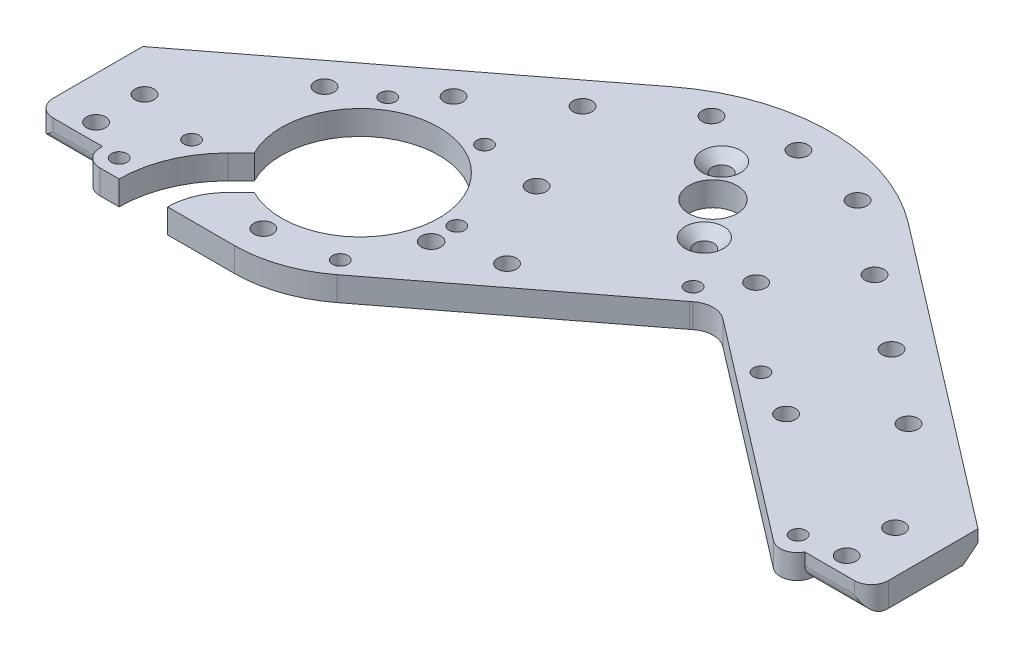
SolidWorks part; units mm, degrees
material "Alum Plate"
ref_plane "Front Plane" through (0, 0, 0) normal (0, 0, 1) x (1, 0, 0)
ref_plane "Top Plane" through (0, 0, 0) normal (0, 1, 0) x (1, 0, 0)
ref_plane "Right Plane" through (0, 0, 0) normal (1, 0, 0) x (0, 0, -1)
sketch "Top Layout" plane through (0, 0, 0) normal (0, 1, 0) x (1, 0, 0)
  line L0 (-114.046, -123.825) -> (-104.775, -123.825) construction
  line L1 (-104.775, -142.875) -> (-101.6, -142.875)
  line L2 (-104.775, -142.875) -> (-104.775, -104.775)
  line L3 (-104.775, -104.775) -> (-101.6, -104.775)
  line L4 (-101.6, -142.875) -> (-101.6, -104.775)
  line L5 (-104.775, -142.875) -> (-101.6, -104.775) construction
  line L6 (-104.775, -104.775) -> (-101.6, -142.875) construction
  line L7 (-19.05, -105.8164) -> (-101.6, -105.8164)
  line L8 (-19.05, -105.8164) -> (-19.05, -141.8336)
  line L9 (-19.05, -141.8336) -> (-101.6, -141.8336)
  line L10 (-101.6, -105.8164) -> (-101.6, -141.8336)
  line L11 (-19.05, -105.8164) -> (-101.6, -141.8336) construction
  line L12 (-19.05, -141.8336) -> (-101.6, -105.8164) construction
  line L13 (-133.096, -85.725) -> (-114.046, -85.725)
  line L14 (-133.096, -85.725) -> (-133.096, -161.925)
  line L15 (-133.096, -161.925) -> (-114.046, -161.925)
  line L16 (-114.046, -85.725) -> (-114.046, -161.925)
  line L17 (-133.096, -85.725) -> (-114.046, -161.925) construction
  line L18 (-133.096, -161.925) -> (-114.046, -85.725) construction
  line L19 (-104.775, -123.825) -> (0, -123.825) construction
  line L20 (0, -123.825) -> (0, 0) construction
  line L21 (-52.3528, -40.1717) -> (0, 0) construction
  line L22 (-70.6449, -16.3328) -> (-18.2922, 23.8388)
  line L23 (-34.0606, -64.0105) -> (18.2922, -23.8388)
  line L24 (-30.9251, 40.3023) -> (-122.2248, -29.7544)
  line L25 (-153.9748, -53.975) -> (-153.9748, -123.825)
  line L26 (-109.5248, -162.052) -> (109.5248, -162.052)
  line L27 (0, -162.052) -> (0, -123.825) construction
  line L28 (-109.5248, -162.052) -> (-109.5248, -20.0093) construction
  line L29 (-104.775, -142.875) -> (-104.775, -152.527)
  line L30 (-104.775, -152.527) -> (104.775, -152.527)
  line L31 (104.775, -104.775) -> (101.6, -104.775)
  line L32 (-144.4498, -73.025) -> (-109.5248, -73.025)
  line L33 (-144.4498, -73.025) -> (-144.4498, -123.825)
  line L34 (-144.4498, -123.825) -> (-109.5248, -123.825) construction
  line L35 (-109.5248, -73.025) -> (-109.5248, -162.052)
  line L36 (-144.4498, -73.025) -> (-109.5248, -123.825) construction
  line L37 (-144.4498, -123.825) -> (-109.5248, -73.025) construction
  line L38 (101.6, -142.875) -> (101.6, -104.775)
  line L39 (104.775, -142.875) -> (101.6, -142.875)
  line L40 (104.775, -142.875) -> (104.775, -104.775)
  line L41 (104.775, -142.875) -> (104.775, -152.527)
  line L42 (109.5248, -162.052) -> (109.5248, -20.0093) construction
  line L43 (30.9251, 40.3023) -> (122.2248, -29.7544)
  line L45 (19.05, -141.8336) -> (101.6, -141.8336)
  line L46 (101.6, -105.8164) -> (101.6, -141.8336)
  line L47 (19.05, -105.8164) -> (101.6, -105.8164)
  line L48 (19.05, -105.8164) -> (19.05, -141.8336)
  line L49 (133.096, -161.925) -> (114.046, -161.925)
  line L50 (114.046, -85.725) -> (114.046, -161.925)
  line L51 (133.096, -85.725) -> (114.046, -85.725)
  line L52 (133.096, -85.725) -> (133.096, -161.925)
  line L53 (144.4498, -123.825) -> (109.5248, -123.825) construction
  line L54 (109.5248, -73.025) -> (109.5248, -162.052)
  line L55 (144.4498, -73.025) -> (109.5248, -73.025)
  line L56 (144.4498, -73.025) -> (144.4498, -123.825)
  line L57 (-109.5248, -123.825) -> (-109.5248, -162.052) construction
  line L62 (-153.9748, -53.975) -> (-122.2248, -53.975)
  line L63 (-122.2248, -53.975) -> (-122.2248, -29.7544)
  line L64 (-144.4498, -123.825) -> (-153.9748, -123.825)
  line L65 (153.9748, -53.975) -> (153.9748, -123.825)
  line L66 (109.5248, -123.825) -> (109.5248, -162.052) construction
  line L67 (144.4498, -123.825) -> (153.9748, -123.825)
  line L68 (122.2248, -29.7544) -> (122.2248, -53.975)
  line L73 (-104.775, -104.775) -> (-104.775, -16.3647) construction
  line L74 (-95.25, -162.052) -> (-95.25, -9.0559) construction
  line L75 (-109.5248, -162.052) -> (-109.5248, -123.825) construction
  line L76 (109.5248, -162.052) -> (109.5248, -123.825) construction
  line L77 (122.2248, -53.975) -> (153.9748, -53.975)
  line L83 (104.775, -155.5496) -> (-104.775, -155.5496) construction
  line L88 (95.25, -162.052) -> (95.25, -9.0559) construction
  line L89 (104.775, -104.775) -> (104.775, -16.3647) construction
  line L92 (-104.775, -152.527) -> (-104.775, -162.052) construction
  line L93 (-14.605, -76.327) -> (14.605, -76.327)
  line L94 (-14.605, -76.327) -> (-14.605, -152.527)
  line L95 (-14.605, -152.527) -> (14.605, -152.527)
  line L96 (14.605, -76.327) -> (14.605, -152.527)
  line L97 (-14.605, -76.327) -> (14.605, -152.527) construction
  line L98 (-14.605, -152.527) -> (14.605, -76.327) construction
  line L99 (104.775, -152.527) -> (104.775, -162.052) construction
  line L100 (-19.05, -105.8164) -> (0, -105.8164) construction
  line L107 (0, -105.8164) -> (19.05, -105.8164) construction
  line L108 (104.775, -123.825) -> (114.046, -123.825) construction
  circle A0 centre (0, 0) radius 114.3
  circle A1 centre (0, 0) radius 6.35
  circle A2 centre (-52.3528, -40.1717) radius 17.8
  circle A3 centre (0, 0) radius 30.0482
  circle A4 centre (-52.3528, -40.1717) radius 30.0482
  arc A5 (-30.9251, 40.3023) -> (30.9251, 40.3023) centre (0, 0) cw
  point P2 (-103.1875, -123.825)
  point P7 (-60.325, -123.825)
  point P12 (-123.571, -123.825)
  point P30 (-126.9873, -98.425)
  point P35 (0, -114.427)
  point P53 (0, -152.527)
  dimension "D1" = 35.6
  dimension "D2" = 12.7
  dimension "D3" = 228.6
  dimension "D11" = 60.0964
  dimension "D12" = 50.8
  dimension "D14" = 52.5
  dimension "D4" = 3.175
  dimension "D5" = 19.05
  dimension "D6" = 76.2
  dimension "D7" = 82.55
  dimension "D8" = 38.1
  dimension "D9" = 104.775
  dimension "D10" = 18.0086
  dimension "D13" = 9.525
  dimension "D15" = 4.7498
  dimension "D16" = 9.525
  dimension "D17" = 9.652
  dimension "D18" = 50.8
  dimension "D19" = 12.446
  dimension "D20" = 65.9892
  dimension "D21" = 19.05
  dimension "D22" = 34.925
  dimension "D23" = 123.825
  dimension "D24" = 12.7
  dimension "D25" = 9.525
  dimension "D26" = 29.21
  dimension "D27" = 76.2
  dimension "D28" = 3.0226
sketch "Side Layout" plane through (0, 0, 0) normal (1, 0, 0) x (0, 0, -1)
  line L0 (0, -38.1) -> (0, 33.7344) construction
  line L1 (-114.3, -20.955) -> (114.3, -20.955)
  line L2 (-114.3, -20.955) -> (-114.3, -33.655)
  line L3 (-114.3, -33.655) -> (114.3, -33.655)
  line L4 (114.3, -20.955) -> (114.3, -33.655)
  line L5 (-114.3, -20.955) -> (114.3, -33.655) construction
  line L6 (-114.3, -33.655) -> (114.3, -20.955) construction
  line L7 (-9.525, -32.9406) -> (9.525, -32.9406)
  line L8 (-9.525, -32.9406) -> (-9.525, -38.1)
  line L9 (-9.525, -38.1) -> (9.525, -38.1)
  line L10 (9.525, -32.9406) -> (9.525, -38.1)
  line L11 (-9.525, -32.9406) -> (9.525, -38.1) construction
  line L12 (-9.525, -38.1) -> (9.525, -32.9406) construction
  line L13 (-11.9126, -29.3338) -> (11.9126, -29.3338)
  line L14 (-11.9126, -29.3338) -> (-11.9126, -32.9406)
  line L15 (-11.9126, -32.9406) -> (11.9126, -32.9406)
  line L16 (11.9126, -29.3338) -> (11.9126, -32.9406)
  line L17 (-11.9126, -29.3338) -> (11.9126, -32.9406) construction
  line L18 (-11.9126, -32.9406) -> (11.9126, -29.3338) construction
  line L19 (-6.35, -32.9406) -> (6.35, -32.9406)
  line L20 (-6.35, -32.9406) -> (-6.35, 33.7344)
  line L21 (-6.35, 33.7344) -> (6.35, 33.7344)
  line L22 (6.35, -32.9406) -> (6.35, 33.7344)
  line L23 (-6.35, -32.9406) -> (6.35, 33.7344) construction
  line L24 (-6.35, 33.7344) -> (6.35, -32.9406) construction
  line L25 (-162.052, 0) -> (-123.825, 0) construction
  line L26 (114.3, -33.655) -> (114.3, 0) construction
  line L27 (-142.875, 19.05) -> (-104.775, 19.05)
  line L28 (-40.1717, -9.525) -> (-40.1717, 5.4) construction
  line L29 (-142.875, 19.05) -> (-142.875, -19.05)
  line L30 (-142.875, -19.05) -> (-104.775, -19.05)
  line L31 (-104.775, 19.05) -> (-104.775, -19.05)
  line L32 (-142.875, 19.05) -> (-104.775, -19.05) construction
  line L33 (-142.875, -19.05) -> (-104.775, 19.05) construction
  line L34 (-130.175, -38.1) -> (-117.9516, -38.1) construction
  line L35 (-57.9717, -14.6) -> (-22.3717, -14.6)
  line L36 (-30.0482, -2.794) -> (30.0482, -2.794)
  line L37 (-30.0482, -2.794) -> (-30.0482, -20.955)
  line L38 (-30.0482, -20.955) -> (30.0482, -20.955)
  line L39 (30.0482, -2.794) -> (30.0482, -20.955)
  line L40 (-30.0482, -2.794) -> (30.0482, -20.955) construction
  line L41 (-30.0482, -20.955) -> (30.0482, -2.794) construction
  line L42 (-30.0482, -2.794) -> (-30.0482, 0) construction
  line L43 (-123.825, 0) -> (0, 0) construction
  line L44 (-57.9717, -14.6) -> (-57.9717, 25.4)
  line L45 (-57.9717, 25.4) -> (-22.3717, 25.4)
  line L46 (-22.3717, -14.6) -> (-22.3717, 25.4)
  line L47 (-19.05, 0) -> (19.05, 0)
  line L48 (-19.05, 0) -> (-19.05, -1.9812)
  line L49 (-19.05, -1.9812) -> (19.05, -1.9812)
  line L50 (19.05, 0) -> (19.05, -1.9812)
  line L51 (-19.05, 0) -> (19.05, -1.9812) construction
  line L52 (-19.05, -1.9812) -> (19.05, 0) construction
  line L53 (-70.2199, -3.175) -> (-10.1235, -3.175)
  line L54 (-70.2199, -3.175) -> (-70.2199, -15.875)
  line L55 (-70.2199, -15.875) -> (-10.1235, -15.875)
  line L56 (-10.1235, -3.175) -> (-10.1235, -15.875)
  line L57 (-70.2199, -3.175) -> (-10.1235, -15.875) construction
  line L58 (-70.2199, -15.875) -> (-10.1235, -3.175) construction
  line L59 (-40.1717, -9.525) -> (-40.1717, 0) construction
  line L60 (-57.9717, -14.6) -> (-22.3717, 25.4) construction
  line L61 (-57.9717, 25.4) -> (-22.3717, -14.6) construction
  line L62 (-22.3717, 0) -> (-57.9717, 0) construction
  line L63 (-137.8162, 0) -> (-123.825, -13.9912) construction
  line L64 (-139.065, 15.24) -> (-108.585, 15.24) construction
  line L65 (-139.065, 15.24) -> (-139.065, -15.24) construction
  line L66 (-139.065, -15.24) -> (-108.585, -15.24) construction
  line L67 (-108.585, 15.24) -> (-108.585, -15.24) construction
  line L68 (-139.065, 15.24) -> (-108.585, -15.24) construction
  line L69 (-139.065, -15.24) -> (-108.585, 15.24) construction
  line L70 (-137.8162, 0) -> (-123.825, 13.9912) construction
  line L71 (-123.825, -13.9912) -> (-109.8338, 0) construction
  line L72 (-123.825, 13.9912) -> (-109.8338, 0) construction
  line L73 (-137.8162, 0) -> (-109.8338, 0) construction
  line L74 (-123.825, -13.9912) -> (-123.825, 13.9912) construction
  line L75 (-6.35, 17.8594) -> (6.35, 17.8594)
  line L76 (114.3, 0) -> (-114.3, 0) construction
  line L77 (-22.3717, 19.05) -> (-6.35, 19.05) construction
  line L78 (-123.825, 38.1) -> (-97.9206, 38.1) construction
  line L79 (-19.05, -3.5814) -> (19.05, -3.5814)
  line L80 (-19.05, -3.5814) -> (-19.05, -1.9812)
  line L81 (-19.05, -1.9812) -> (19.05, -1.9812)
  line L82 (19.05, -3.5814) -> (19.05, -1.9812)
  line L83 (-19.05, -3.5814) -> (19.05, -1.9812) construction
  line L84 (-19.05, -1.9812) -> (19.05, -3.5814) construction
  line L85 (-8.7376, -16.7608) -> (8.7376, -16.7608)
  line L86 (-8.7376, -16.7608) -> (-8.7376, -29.3338)
  line L87 (-8.7376, -29.3338) -> (8.7376, -29.3338)
  line L88 (8.7376, -16.7608) -> (8.7376, -29.3338)
  line L89 (-8.7376, -16.7608) -> (8.7376, -29.3338) construction
  line L90 (-8.7376, -29.3338) -> (8.7376, -16.7608) construction
  line L91 (-8.7376, -3.5814) -> (8.7376, -3.5814)
  line L92 (-8.7376, -3.5814) -> (-8.7376, -16.1544)
  line L93 (-8.7376, -16.1544) -> (8.7376, -16.1544)
  line L94 (8.7376, -3.5814) -> (8.7376, -16.1544)
  line L95 (-8.7376, -3.5814) -> (8.7376, -16.1544) construction
  line L96 (-8.7376, -16.1544) -> (8.7376, -3.5814) construction
  circle A0 centre (-123.825, 0) radius 18.0086
  circle A1 centre (-123.825, 0) radius 38.1
  circle A2 centre (-139.065, 15.24) radius 1.905
  circle A3 centre (-108.585, 15.24) radius 1.905
  circle A4 centre (-108.585, -15.24) radius 1.905
  circle A5 centre (-139.065, -15.24) radius 1.905
  circle A6 centre (-137.8162, 0) radius 1.6002
  circle A7 centre (-123.825, 13.9912) radius 1.6002
  circle A8 centre (-109.8338, 0) radius 1.6002
  circle A9 centre (-123.825, -13.9912) radius 1.6002
  point P0 (0, -27.305)
  point P6 (0, -31.1372)
  point P7 (0, -35.5203)
  point P21 (0, 0.3969)
  point P32 (0, -11.8745)
  point P43 (0, -0.9906)
  point P55 (-40.1717, -9.525)
  point P72 (-40.1717, 5.4)
  point P88 (0, -23.0473)
  point P93 (0, -2.7813)
  point P102 (0, -9.8679)
  dimension "D17" = 3.81
  dimension "D18" = 3.2004
  dimension "D1" = 12.7
  dimension "D2" = 5.1594
  dimension "D3" = 19.05
  dimension "D4" = 3.6068
  dimension "D5" = 23.8252
  dimension "D6" = 12.7
  dimension "D7" = 18.161
  dimension "D8" = 1.9812
  dimension "D9" = 12.7
  dimension "D10" = 40
  dimension "D11" = 25.4
  dimension "D12" = 50.8
  dimension "D13" = 41.275
  dimension "D14" = 30.48
  dimension "D15" = 4.445
  dimension "D16" = 19.7866
  dimension "D19" = 15.875
  dimension "D20" = 6.35
  dimension "D21" = 38.1
  dimension "D22" = 1.6002
  dimension "D23" = 38.1
  dimension "D24" = 17.4752
  dimension "D25" = 12.573
ref_plane "Plane1" through (0, 25.4, 0) normal (0, 1, 0) x (1, 0, 0)
sketch "Sketch3" plane through (0, 25.4, 0) normal (0, 1, 0) x (1, 0, 0)
  line L0 (-104.775, -36.3747) -> (-30.9251, 20.2924)
  line L1 (-104.775, -104.775) -> (-104.775, -16.3647) construction
  line L2 (0, -200130.175) -> (0, 199882.0484) construction
  line L3 (-30.9251, 40.3023) -> (-122.2248, -29.7544) construction
  line L5 (-104.775, -36.3747) -> (-104.775, -77.6497)
  line L6 (-92.075, -77.6497) -> (-104.775, -77.6497)
  line L7 (30.9251, 20.2924) -> (104.775, -36.3747)
  line L8 (104.775, -77.6497) -> (92.075, -77.6497)
  line L9 (104.775, -36.3747) -> (104.775, -77.6497)
  line L11 (104.775, -104.775) -> (104.775, -16.3647) construction
  line L12 (30.9251, 40.3023) -> (122.2248, -29.7544) construction
  line L13 (92.075, -74.6536) -> (24.1423, -22.5271)
  line L14 (-32.2514, -66.3682) -> (20.1013, -26.1965)
  line L15 (-30.9251, 20.2924) -> (0, 44.022)
  line L16 (0, 44.022) -> (30.9251, 20.2924)
  line L17 (-92.075, -77.6497) -> (-92.075, -73.1917)
  line L19 (-92.075, -73.1917) -> (-52.3528, -73.1917)
  line L20 (92.075, -74.6536) -> (92.075, -77.6497)
  circle A1 centre (-52.3528, -40.1717) radius 20.6375
  circle A2 centre (0, 0) radius 6.35
  circle A3 centre (0, 0) radius 6.35 construction
  arc A4 (-52.3528, -73.1917) -> (-32.2514, -66.3682) centre (-52.3528, -40.1717) ccw
  arc A5 (20.1013, -26.1965) -> (24.1423, -22.5271) centre (0, 0) ccw
  arc A6 (30.9251, 20.2924) -> (-30.9251, 20.2924) centre (0, -20.01) ccw construction
  point P28 (0, 44.022)
  dimension "D1" = 33.02
  dimension "D5" = 50.8
  dimension "D7" = 41.275
  dimension "D2" = 41.275
  dimension "D3" = 34.925
  dimension "D4" = 12.7
  dimension "D6" = 38.1
extrude "Boss-Extrude1" add sketch "Sketch3" against normal blind 6.35
ref_plane "Plane3" through (-104.775, 0, 0) normal (-1, 0, 0) x (0, 0, 1)
sketch "Sketch6" plane through (-104.775, 0, 0) normal (-1, 0, 0) x (0, 0, 1)
  line L0 (162.052, -25.4) -> (162.052, 25.4)
  line L1 (162.052, 25.4) -> (77.6497, 25.4)
  line L2 (36.3747, 25.4) -> (77.6497, 25.4) construction
  line L3 (147.7645, 11.1125) -> (162.052, 11.1125) construction
  line L4 (162.052, 0) -> (71.2997, 0) construction
  line L5 (77.6497, 25.4) -> (77.6497, 19.05)
  line L6 (77.6497, 19.05) -> (36.3747, 19.05)
  line L7 (36.3747, 19.05) -> (36.3747, 6.35)
  line L8 (36.3747, 6.35) -> (71.2997, 6.35)
  line L10 (99.6315, -3.175) -> (99.6315, 11.1125) construction
  line L11 (71.2997, -25.4) -> (162.052, -25.4)
  line L13 (71.2997, 6.35) -> (71.2997, -25.4)
  line L14 (152.527, -25.4) -> (152.527, 25.4) construction
  line L15 (99.6315, 11.1125) -> (99.6315, 25.4) construction
  line L16 (147.7645, 11.1125) -> (147.7645, 25.4) construction
  line L17 (94.869, -7.9375) -> (104.394, -7.9375) construction
  line L18 (94.869, -7.9375) -> (94.869, 25.4) construction
  line L19 (94.869, 25.4) -> (104.394, 25.4) construction
  line L20 (104.394, -7.9375) -> (104.394, 25.4) construction
  line L21 (94.869, -7.9375) -> (104.394, 25.4) construction
  line L22 (94.869, 25.4) -> (104.394, -7.9375) construction
  line L23 (147.7645, 11.1125) -> (147.7645, -3.175) construction
  line L24 (104.394, -7.9375) -> (123.825, -7.9375) construction
  line L25 (143.002, -7.9375) -> (152.527, -7.9375) construction
  line L26 (143.002, -7.9375) -> (143.002, 25.4) construction
  line L27 (143.002, 25.4) -> (152.527, 25.4) construction
  line L28 (152.527, -7.9375) -> (152.527, 25.4) construction
  line L29 (143.002, -7.9375) -> (152.527, 25.4) construction
  line L30 (143.002, 25.4) -> (152.527, -7.9375) construction
  line L31 (123.825, -7.9375) -> (152.527, -7.9375) construction
  line L32 (104.775, 19.05) -> (104.775, -19.05) construction
  line L34 (155.702, -25.4) -> (155.702, 25.4) construction
  circle A0 centre (109.8338, 0) radius 1.6002 construction
  circle A1 centre (123.825, 13.9912) radius 1.6002 construction
  circle A2 centre (137.8162, 0) radius 1.6002 construction
  circle A3 centre (123.825, -13.9912) radius 1.6002 construction
  circle A4 centre (109.8338, 0) radius 1.6002 construction
  circle A5 centre (123.825, 13.9912) radius 1.6002 construction
  circle A6 centre (137.8162, 0) radius 1.6002 construction
  circle A7 centre (123.825, -13.9912) radius 1.6002 construction
  circle A8 centre (123.825, 0) radius 18.0086 construction
  circle A9 centre (123.825, 0) radius 18.0086 construction
  circle A10 centre (123.825, 0) radius 9.525
  circle A11 centre (108.585, -15.24) radius 1.905 construction
  circle A12 centre (108.585, 15.24) radius 1.905 construction
  circle A13 centre (139.065, 15.24) radius 1.905 construction
  circle A14 centre (139.065, -15.24) radius 1.905 construction
  circle A15 centre (108.585, -15.24) radius 1.905
  circle A16 centre (108.585, 15.24) radius 1.905
  circle A17 centre (139.065, 15.24) radius 1.905
  circle A18 centre (139.065, -15.24) radius 1.905
  circle A19 centre (147.7645, 11.1125) radius 2.5527
  circle A26 centre (99.6315, 11.1125) radius 2.5527
  circle A27 centre (99.6315, -3.175) radius 2.5527
  circle A28 centre (147.7645, -3.175) radius 2.5527
  point P29 (0, 0)
  point P55 (99.6315, 8.7312)
  point P61 (147.7645, 8.7312)
  dimension "D4" = 19.05
  dimension "D7" = 5.1054
  dimension "D1" = 6.35
  dimension "D2" = 12.7
  dimension "D3" = 25.4
  dimension "D5" = 6.35
  dimension "D6" = 3.175
  dimension "D8" = 0.381
  dimension "D9" = 14.2875
  dimension "D10" = 9.525
  dimension "D12" = 33.3375
sketch "Sketch12" [suppressed] plane through (0, 19.05, 0) normal (0, 1, 0) x (1, 0, 0)
  line L0 (-104.775, -77.6497) -> (-104.775, -36.3747)
  line L1 (-104.775, -36.3747) -> (-92.075, -36.3747)
  line L3 (-92.075, -36.3747) -> (-92.075, -77.6497)
  line L5 (-92.075, -77.6497) -> (-104.775, -77.6497)
  line L6 (-98.425, -77.6497) -> (-98.425, -63.3622) construction
  line L7 (-98.425, -63.3622) -> (-98.425, -50.6622) construction
  line L8 (-98.425, -50.6622) -> (-98.425, -36.3747) construction
  line L10 (-98.425, -36.3747) -> (-104.775, -36.3747) construction
  circle A0 centre (-98.425, -63.3622) radius 2.5527
  circle A1 centre (-98.425, -50.6622) radius 2.5527
  dimension "D2" = 5.1054
  dimension "D1" = 12.7
  dimension "D3" = 12.7
sketch "Sketch8" plane through (0, 25.4, 0) normal (0, 1, 0) x (1, 0, 0)
  line L0 (-109.5248, -162.052) -> (-109.5248, -20.0093) construction
  line L1 (-104.775, -77.6497) -> (-109.5248, -77.6497)
  line L2 (-104.775, -77.6497) -> (-104.775, -36.3747)
  line L3 (-104.775, -36.3747) -> (-109.5248, -36.3747)
  line L4 (-109.5248, -77.6497) -> (-109.5248, -36.3747)
  line L5 (-104.775, -77.6497) -> (-109.5248, -36.3747) construction
  line L6 (-104.775, -36.3747) -> (-109.5248, -77.6497) construction
  line L7 (104.775, -77.6497) -> (109.5248, -77.6497)
  line L8 (104.775, -77.6497) -> (104.775, -36.3747)
  line L9 (104.775, -36.3747) -> (109.5248, -36.3747)
  line L10 (109.5248, -77.6497) -> (109.5248, -36.3747)
  line L11 (104.775, -77.6497) -> (109.5248, -36.3747) construction
  line L12 (104.775, -36.3747) -> (109.5248, -77.6497) construction
  point P4 (-107.1499, -57.0122)
  point P10 (107.1499, -57.0122)
extrude "Boss-Extrude4" add sketch "Sketch8" against normal through all
sketch "Sketch9" plane through (0, 25.4, 0) normal (0, 1, 0) x (1, 0, 0)
  line L0 (7.4916, -9.7632) -> (0, 0) construction
  line L1 (0, 0) -> (-7.4916, 9.7632) construction
  line L2 (0, 44.022) -> (-104.775, -36.3747) construction
  circle A0 centre (-7.4916, 9.7632) radius 2.4892
  circle A1 centre (7.4916, -9.7632) radius 2.4892
  dimension "D2" = 4.9784
  dimension "D1" = 24.6126
extrude "Collar Holes" cut sketch "Sketch9" against normal through all
sketch "Sketch10" plane through (0, 25.4, 0) normal (0, 1, 0) x (1, 0, 0)
  line L0 (0, 33.4567) -> (0, 30.79) construction
  line L1 (-5.1026, 40.1066) -> (0, 33.4567) construction
  line L2 (0, 33.4567) -> (5.1026, 40.1066) construction
  line L3 (0, 44.022) -> (-104.775, -36.3747) construction
  line L4 (104.775, -36.3747) -> (0, 44.022) construction
  circle A0 centre (0, 33.4567) radius 4.7625 construction
  circle A1 centre (0, 33.4567) radius 2.0193
  arc A3 (30.9251, 20.2924) -> (-30.9251, 20.2924) centre (0, -20.01) ccw construction
  dimension "D2" = 9.525
  dimension "D3" = 4.0386
  dimension "D1" = 8.382
extrude "Spacer Holes" cut sketch "Sketch10" against normal through all
pattern_linear "Spacer Hole Pattern" count 5 spacing 24.13 along (-0.7934, 0, 0.6088) of "Spacer Holes"
mirror "Spacer Hole Mirror" about plane through (0, 0, 0) normal (1, 0, 0) of "Spacer Hole Pattern"
sketch "Sketch16" plane through (0, 25.4, 0) normal (0, 1, 0) x (1, 0, 0)
  line L0 (-109.5248, -50.6622) -> (-98.425, -50.6622) construction
  line L1 (-109.5248, -36.3747) -> (-109.5248, -77.6497) construction
  line L2 (-98.425, -50.6622) -> (-98.425, -63.3622) construction
  line L3 (-98.425, -63.3622) -> (-109.5248, -63.3622) construction
  line L4 (-98.425, -63.3622) -> (-98.425, -77.6497) construction
  line L5 (-109.5248, -77.6497) -> (-92.075, -77.6497) construction
  line L6 (-98.425, -50.6622) -> (-98.425, -36.3747) construction
  line L7 (-104.775, -36.3747) -> (-109.5248, -36.3747) construction
  line L8 (-104.775, -36.3747) -> (-104.775, -77.6497) construction
  line L9 (0, 0) -> (0, 30.79) construction
  line L10 (104.775, -36.3747) -> (104.775, -77.6497) construction
  circle A0 centre (-98.425, -50.6622) radius 2.0193
  circle A1 centre (-98.425, -63.3622) radius 2.0193
  circle A4 centre (98.425, -63.3622) radius 2.0193
  circle A5 centre (98.425, -50.6622) radius 2.0193
  arc A6 (30.9251, 20.2924) -> (-30.9251, 20.2924) centre (0, -20.01) ccw construction
  dimension "D1" = 4.0386
  dimension "D2" = 12.7
  dimension "D3" = 6.35
extrude "Custom Nutstrip Holes" cut sketch "Sketch16" against normal through all
sketch "Sketch36" plane through (0, 25.4, 0) normal (0, 1, 0) x (1, 0, 0)
  line L0 (-52.3528, -65.5717) -> (-12.44, -41.5615) construction
  line L1 (-12.44, -41.5615) -> (24.5129, -13.2066) construction
  line L2 (24.5129, -13.2066) -> (58.2939, -39.1277) construction
  line L3 (-32.2514, -66.3682) -> (20.1013, -26.1965) construction
  line L4 (24.1423, -22.5271) -> (92.075, -74.6536) construction
  line L5 (-12.44, -41.5615) -> (-7.8012, -47.6069) construction
  line L6 (58.2939, -39.1277) -> (53.6552, -45.1731) construction
  line L7 (-52.3528, -65.5717) -> (-52.3528, -40.1717) construction
  line L8 (58.2939, -39.1277) -> (92.075, -65.0488) construction
  line L9 (92.075, -65.0488) -> (92.075, -77.6497) construction
  line L10 (-52.3528, -40.1717) -> (-26.1764, -20.0858) construction
  line L11 (-26.1764, -20.0858) -> (0, 0) construction
  line L12 (92.075, -74.6536) -> (92.075, -77.6497) construction
  circle A0 centre (-52.3528, -65.5717) radius 2.0193
  circle A1 centre (58.2939, -39.1277) radius 2.0193
  circle A2 centre (24.5129, -13.2066) radius 2.0193
  circle A3 centre (-12.44, -41.5615) radius 2.0193
  circle A4 centre (-76.5745, -25.3009) radius 2.0193 construction
  circle A5 centre (-52.3528, -65.5717) radius 4.7625 construction
  circle A6 centre (-12.44, -41.5615) radius 4.7625 construction
  circle A7 centre (24.5129, -13.2066) radius 4.7625 construction
  circle A8 centre (58.2939, -39.1277) radius 4.7625 construction
  arc A9 (-52.3528, -73.1917) -> (-32.2514, -66.3682) centre (-52.3528, -40.1717) ccw construction
  circle A10 centre (-26.1764, -20.0858) radius 2.0193
  dimension "D1" = 9.525
  dimension "D2" = 25.4
  dimension "D3" = 7.62
extrude "Aux Spacer Holes" cut sketch "Sketch36" against normal through all
sketch "Sketch38" [suppressed] plane through (-104.775, 0, 0) normal (-1, 0, 0) x (0, 0, 1)
  line L1 (152.527, -7.9375) -> (143.002, -7.9375)
  line L2 (152.527, -7.9375) -> (152.527, 25.4)
  line L3 (152.527, 25.4) -> (143.002, 25.4)
  line L4 (143.002, -7.9375) -> (143.002, 25.4)
  line L5 (152.527, -7.9375) -> (143.002, 25.4) construction
  line L6 (152.527, 25.4) -> (143.002, -7.9375) construction
  point P4 (147.7645, 8.7312)
extrude "Cut-Extrude16" [suppressed] cut sketch "Sketch38" against normal blind 9.525
sketch "Sketch46" [suppressed] plane through (-104.775, 0, 0) normal (-1, 0, 0) x (0, 0, 1)
  line L0 (142.875, 19.05) -> (104.775, -19.05) construction
  line L1 (104.14, 19.685) -> (143.51, 19.685)
  line L2 (104.14, 19.685) -> (104.14, -19.685)
  line L3 (104.14, -19.685) -> (143.51, -19.685)
  line L4 (143.51, 19.685) -> (143.51, -19.685)
  line L5 (104.14, 19.685) -> (143.51, -19.685) construction
  line L6 (104.14, -19.685) -> (143.51, 19.685) construction
  point P0 (123.825, 0)
  dimension "D1" = 39.37
extrude "Cut-Extrude21" [suppressed] cut sketch "Sketch46" against normal blind 6.985
ref_plane "Plane5" through (0, 0, 152.527) normal (0, 0, 1) x (1, 0, 0)
sketch "Sketch41" plane through (0, 0, 152.527) normal (0, 0, 1) x (1, 0, 0)
  line L0 (-104.775, -7.9375) -> (-104.775, 25.4) construction
  line L1 (-104.775, -7.9375) -> (-104.775, 12.7)
  line L2 (-104.775, -7.9375) -> (104.775, -7.9375)
  line L3 (104.775, -7.9375) -> (104.775, 12.7)
  line L4 (104.775, 25.4) -> (-104.775, 25.4)
  line L5 (0, -7.9375) -> (0, 25.4) construction
  line L6 (-104.775, 3.9624) -> (-100.0125, 3.9624) construction
  line L7 (-100.0125, 3.9624) -> (-100.0125, 25.4) construction
  line L8 (104.775, 3.9624) -> (100.0125, 3.9624) construction
  line L9 (100.0125, 3.9624) -> (100.0125, 25.4) construction
  line L10 (19.05, 20.6375) -> (23.8252, 20.6375) construction
  line L11 (19.05, 15.875) -> (78.5876, 15.875) construction
  line L12 (19.05, 15.875) -> (19.05, 25.4) construction
  line L13 (19.05, 25.4) -> (78.5876, 25.4) construction
  line L14 (78.5876, 15.875) -> (78.5876, 25.4) construction
  line L15 (19.05, 15.875) -> (78.5876, 25.4) construction
  line L16 (19.05, 25.4) -> (78.5876, 15.875) construction
  line L17 (23.8252, 20.6375) -> (38.1127, 20.6375) construction
  line L18 (38.1127, 20.6375) -> (52.4002, 20.6375) construction
  line L19 (52.4002, 20.6375) -> (66.6877, 20.6375) construction
  line L20 (-104.775, 25.4) -> (-112.395, 25.4)
  line L21 (-112.395, 25.4) -> (-112.395, 3.175)
  line L22 (-112.395, 3.175) -> (-109.5248, 3.175)
  line L23 (-109.5248, 3.175) -> (-109.5248, 12.7)
  line L24 (-109.5248, 12.7) -> (-104.775, 12.7)
  line L25 (-104.775, 12.7) -> (-104.775, 25.4) construction
  line L26 (104.775, 25.4) -> (112.395, 25.4)
  line L27 (112.395, 25.4) -> (112.395, 3.175)
  line L28 (112.395, 3.175) -> (109.5248, 3.175)
  line L29 (109.5248, 3.175) -> (109.5248, 12.7)
  line L30 (109.5248, 12.7) -> (104.775, 12.7)
  line L31 (104.775, 12.7) -> (104.775, 25.4) construction
  line L32 (-100.0125, 3.9624) -> (-87.3125, 3.9624) construction
  line L33 (-63.5, -1.5875) -> (0, -1.5875) construction
  line L34 (0, -1.5875) -> (63.5, -1.5875) construction
  line L35 (63.5, -1.5875) -> (63.5, -7.9375) construction
  circle A0 centre (-100.0125, 3.9624) radius 2.5527
  circle A1 centre (100.0125, 3.9624) radius 2.5527
  circle A2 centre (23.8252, 20.6375) radius 2.5527
  circle A3 centre (38.1127, 20.6375) radius 2.5527
  circle A4 centre (52.4002, 20.6375) radius 2.5527
  circle A5 centre (66.6877, 20.6375) radius 2.5527
  circle A6 centre (-66.6877, 20.6375) radius 2.5527
  circle A7 centre (-52.4002, 20.6375) radius 2.5527
  circle A8 centre (-38.1127, 20.6375) radius 2.5527
  circle A9 centre (-23.8252, 20.6375) radius 2.5527
  circle A10 centre (-87.3125, 3.9624) radius 2.5527
  circle A11 centre (87.3125, 3.9624) radius 2.5527
  circle A12 centre (-63.5, -1.5875) radius 2.5527
  circle A13 centre (63.5, -1.5875) radius 2.5527
  point P14 (48.8188, 20.6375)
  dimension "D3" = 5.1054
  dimension "D7" = 5.1054
  dimension "D1" = 21.4376
  dimension "D2" = 4.7625
  dimension "D4" = 9.525
  dimension "D5" = 59.5376
  dimension "D6" = 4.7752
  dimension "D8" = 14.2875
  dimension "D9" = 7.62
  dimension "D10" = 4.7498
  dimension "D11" = 12.7
  dimension "D12" = 9.525
  dimension "D13" = 19.05
  dimension "D14" = 12.7
  dimension "D15" = 6.35
  dimension "D16" = 63.5
sketch "Sketch43" [suppressed] plane through (-109.5248, 0, 0) normal (-1, 0, 0) x (0, 0, 1)
  line L1 (152.527, 12.7) -> (155.702, 12.7)
  line L2 (152.527, 12.7) -> (152.527, 25.4)
  line L3 (152.527, 25.4) -> (155.702, 25.4)
  line L4 (155.702, 12.7) -> (155.702, 25.4)
  line L5 (152.527, 12.7) -> (155.702, 25.4) construction
  line L6 (152.527, 25.4) -> (155.702, 12.7) construction
  line L7 (162.052, 25.4) -> (77.6497, 25.4) construction
  point P4 (154.1145, 19.05)
  dimension "D1" = 3.175
sketch "Sketch44" plane through (0, 25.4, 0) normal (0, 1, 0) x (1, 0, 0)
  line L0 (73.8315, -147.7645) -> (73.8315, -152.527) construction
  line L1 (92.075, -74.6536) -> (92.075, -77.6497) construction
  line L2 (-92.075, -77.6497) -> (-92.075, -73.1917) construction
  line L3 (0, -123.825) -> (0, 0) construction
  line L4 (-92.075, -73.1917) -> (-52.3528, -73.1917) construction
  line L5 (-104.775, -104.775) -> (-104.775, -16.3647) construction
  line L6 (-32.2514, -66.3682) -> (20.1013, -26.1965) construction
  line L21 (-104.775, -68.1247) -> (-104.775, -152.527)
  line L22 (-104.775, -152.527) -> (104.775, -152.527)
  line L23 (104.775, -152.527) -> (104.775, -68.1247)
  line L34 (-104.775, -99.6315) -> (-100.0125, -99.6315) construction
  line L35 (-104.775, -147.7645) -> (-100.0125, -147.7645) construction
  line L36 (0, -152.527) -> (0, -35.6178) construction
  line L38 (30.969, -147.7645) -> (45.2565, -147.7645) construction
  line L39 (45.2565, -147.7645) -> (59.544, -147.7645) construction
  line L40 (59.544, -147.7645) -> (73.8315, -147.7645) construction
  line L41 (23.8252, -152.527) -> (30.969, -152.527) construction
  line L42 (104.775, -152.527) -> (-104.775, -152.527) construction
  line L43 (30.969, -152.527) -> (38.1127, -152.527) construction
  line L44 (30.969, -152.527) -> (30.969, -147.7645) construction
  line L45 (-92.075, -77.6497) -> (-104.775, -77.6497) construction
  line L48 (-35.1507, -62.5899) -> (-8.9743, -42.504) construction
  line L49 (-8.9743, -42.504) -> (17.2021, -22.4182) construction
  line L50 (45.5313, -32.9364) -> (87.3125, -64.9962) construction
  line L51 (92.075, -74.6536) -> (24.1423, -22.5271) construction
  line L52 (104.775, -77.6497) -> (92.075, -77.6497) construction
  line L79 (-104.775, -68.1247) -> (-92.075, -68.1247)
  line L80 (-92.075, -68.1247) -> (-92.075, -63.6667)
  line L85 (21.8118, -8.7328) -> (92.075, -62.6476)
  line L86 (-38.0499, -58.8115) -> (14.3028, -18.6398)
  line L87 (-92.075, -63.6667) -> (-52.3528, -63.6667)
  line L88 (92.075, -62.6476) -> (92.075, -68.1247)
  line L89 (92.075, -68.1247) -> (104.775, -68.1247)
  circle A0 centre (-73.8315, -147.7645) radius 2.5527
  circle A1 centre (-59.544, -147.7645) radius 2.5527
  circle A2 centre (-45.2565, -147.7645) radius 2.5527
  circle A3 centre (-30.969, -147.7645) radius 2.5527
  circle A17 centre (-100.0125, -99.6315) radius 2.5527
  circle A18 centre (-100.0125, -147.7645) radius 2.5527
  circle A19 centre (100.0125, -147.7645) radius 2.5527
  circle A20 centre (100.0125, -99.6315) radius 2.5527
  circle A21 centre (30.969, -147.7645) radius 2.5527
  circle A22 centre (45.2565, -147.7645) radius 2.5527
  circle A23 centre (59.544, -147.7645) radius 2.5527
  circle A24 centre (73.8315, -147.7645) radius 2.5527
  circle A25 centre (-87.3125, -68.4292) radius 4.7625 construction
  circle A26 centre (-35.1507, -62.5899) radius 4.7625 construction
  circle A27 centre (-8.9743, -42.504) radius 4.7625 construction
  circle A28 centre (17.2021, -22.4182) radius 4.7625 construction
  circle A29 centre (45.5313, -32.9364) radius 4.7625 construction
  circle A30 centre (87.3125, -64.9962) radius 4.7625 construction
  circle A32 centre (-87.3125, -68.4292) radius 2.5527
  circle A33 centre (-35.1507, -62.5899) radius 2.5527
  circle A34 centre (-8.9743, -42.504) radius 2.5527 construction
  circle A35 centre (17.2021, -22.4182) radius 2.5527
  circle A36 centre (45.5313, -32.9364) radius 2.5527
  circle A37 centre (87.3125, -64.9962) radius 2.5527
  circle A38 centre (-97.155, -85.2697) radius 7.62 construction
  circle A39 centre (97.155, -85.2697) radius 7.62 construction
  circle A40 centre (24.5121, -32.4156) radius 7.62 construction
  arc A41 (20.1013, -26.1965) -> (24.1423, -22.5271) centre (0, 0) ccw construction
  circle A42 centre (-97.155, -85.2697) radius 2.5527
  circle A43 centre (24.5121, -32.4156) radius 2.5527
  circle A44 centre (97.155, -85.2697) radius 2.5527
  arc A56 (14.3028, -18.6398) -> (21.8118, -8.7328) centre (0, 0) ccw
  arc A57 (-52.3528, -63.6667) -> (-38.0499, -58.8115) centre (-52.3528, -40.1717) ccw
  point P4 (-104.775, -152.527)
  dimension "D2" = 5.1054
  dimension "D7" = 5.1054
  dimension "D8" = 15.24
  dimension "D3" = 9.525
  dimension "D9" = 9.525
  dimension "D4" = 4.7625
  dimension "D5" = 14.2875
  dimension "D6" = 9.525
  dimension "D1" = 4.7625
  dimension "D10" = 52.664
sketch "Sketch82" [suppressed] plane through (0, 28.829, 0) normal (0, 1, 0) x (1, 0, 0)
  line L0 (-52.3528, -63.6667) -> (-92.075, -63.6667) construction
  line L1 (-52.3528, -65.5717) -> (-52.3528, -63.6667) construction
  line L2 (-12.4467, -41.5667) -> (-13.6064, -40.0553) construction
  line L3 (14.3028, -18.6398) -> (-38.0499, -58.8115) construction
  line L4 (24.5175, -13.2101) -> (25.6772, -11.6988) construction
  line L5 (92.075, -62.6476) -> (21.8118, -8.7328) construction
  line L6 (58.2962, -39.1295) -> (59.4559, -37.6181) construction
  line L7 (21.4643, -9.5551) -> (21.8118, -8.7328)
  line L8 (21.8118, -8.7328) -> (22.2143, -9.0416)
  circle A0 centre (-52.3528, -65.5717) radius 4.7625
  circle A1 centre (-12.4467, -41.5667) radius 4.7625
  arc A2 (21.4643, -9.5551) -> (22.2143, -9.0416) centre (24.5175, -13.2101) ccw
  circle A3 centre (58.2962, -39.1295) radius 4.7625
  arc A4 (14.3028, -18.6398) -> (21.8118, -8.7328) centre (0, 0) ccw construction
  dimension "D1" = 9.525
  dimension "D2" = 1.905
  dimension "D3" = 30.8104
  dimension "D4" = 83.6926
  dimension "D5" = 41.1154
extrude "Cut-Extrude38" [suppressed] cut sketch "Sketch82" against normal up to surface (3.429 mm away)
sketch "Sketch45" [suppressed] plane through (0, -25.4, 0) normal (0, -1, 0) x (1, 0, 0)
  circle A2 centre (24.5121, 32.4156) radius 6.35
  circle A4 centre (-97.155, 85.2697) radius 6.35
  circle A5 centre (97.155, 85.2697) radius 6.35
  dimension "D1" = 12.7
ref_plane "Plane6" through (0, 19.05, 0) normal (0, 1, 0) x (1, 0, 0)
sketch "Sketch59" [suppressed] plane through (0, 19.05, 0) normal (0, 1, 0) x (1, 0, 0)
  line L0 (0, 22.408) -> (0, 30.79) construction
  line L1 (-19.1436, 18.7673) -> (-24.2463, 25.4172) construction
  line L2 (0, 33.4567) -> (-5.1026, 40.1066) construction
  line L3 (-5.1026, 40.1066) -> (-24.2463, 25.4172) construction
  line L4 (-104.775, -36.3747) -> (-30.9251, 20.2924) construction
  line L5 (-19.1436, 18.7673) -> (0, 33.4567) construction
  circle A0 centre (0, 22.408) radius 4.7625
  circle A2 centre (-19.1436, 18.7673) radius 4.7625
  arc A3 (30.9251, 20.2924) -> (-30.9251, 20.2924) centre (0, -20.01) ccw construction
  dimension "D3" = 9.525
  dimension "D1" = 8.382
  dimension "D2" = 24.13
sketch "Sketch47" plane through (0, 25.4, 0) normal (0, 1, 0) x (1, 0, 0)
  line L0 (-21.3485, -42.7945) -> (-23.7291, -44.6212) construction
  line L1 (-81.9672, -61.1267) -> (-75.3534, -61.1267) construction
  line L2 (-19.1436, 18.7673) -> (-38.2872, 4.0779) construction
  line L3 (-38.2872, 4.0779) -> (-57.4308, -10.6115) construction
  line L4 (-57.4308, -10.6115) -> (-76.5745, -25.3009) construction
  line L5 (-19.1436, 18.7673) -> (0, 33.4567) construction
  line L6 (-76.5745, -25.3009) -> (-65.8758, -19.4248) construction
  line L7 (-65.8758, -19.4248) -> (-57.4308, -10.6115) construction
  line L9 (-87.7466, -52.146) -> (-71.6552, -16.7941)
  line L10 (-38.0499, -58.8115) -> (14.3028, -18.6398) construction
  line L11 (-81.9672, -54.7767) -> (-52.3528, -40.1717) construction
  line L12 (-52.3528, -40.1717) -> (-65.8758, -19.4248) construction
  line L13 (-92.075, -63.6667) -> (-52.3528, -63.6667) construction
  line L14 (-70.5066, -49.3452) -> (-83.977, -62.8156) construction
  line L15 (-23.7291, -44.6212) -> (-39.5962, -56.7964)
  line L16 (-52.3528, -61.1267) -> (-81.9672, -61.1267)
  line L17 (-42.4227, -17.4847) -> (-52.3528, -40.1717) construction
  line L18 (-52.3528, -40.1717) -> (-27.5947, -39.5834) construction
  line L19 (-81.9672, -54.7767) -> (-65.8758, -19.4248) construction
  line L20 (-65.8758, -19.4248) -> (-42.4227, -17.4847) construction
  line L21 (-42.4227, -17.4847) -> (-27.5947, -39.5834) construction
  line L22 (-83.977, -62.8156) -> (-74.9967, -71.7959) construction
  line L23 (-74.9967, -71.7959) -> (-61.5263, -58.3255) construction
  line L24 (-79.4868, -67.3058) -> (-52.3528, -40.1717) construction
  line L25 (-52.3528, -60.5117) -> (-52.3528, -40.1717) construction
  arc A0 (-87.7466, -52.146) -> (-81.9672, -61.1267) centre (-81.9672, -54.7767) ccw
  arc A1 (-23.7291, -44.6212) -> (-27.4458, -33.2351) centre (-27.5947, -39.5834) ccw
  arc A2 (-60.2505, -16.4788) -> (-71.6552, -16.7941) centre (-65.8758, -19.4248) ccw
  arc A3 (-36.4919, -19.7535) -> (-48.4556, -15.5031) centre (-42.4227, -17.4847) ccw
  arc A4 (-21.3485, -42.7945) -> (-75.3534, -61.1267) centre (-52.3528, -40.1717) ccw construction
  arc A5 (-52.3528, -63.6667) -> (-38.0499, -58.8115) centre (-52.3528, -40.1717) ccw construction
  arc A6 (-52.3528, -61.1267) -> (-39.5962, -56.7964) centre (-52.3528, -40.1717) ccw
  circle A7 centre (-81.9672, -54.7767) radius 2.4892
  circle A8 centre (-65.8758, -19.4248) radius 2.4892
  circle A9 centre (-42.4227, -17.4847) radius 2.4892
  circle A10 centre (-27.5947, -39.5834) radius 2.4892
  circle A11 centre (-52.3528, -40.1717) radius 6.985
  arc A13 (-60.2505, -16.4788) -> (-48.4556, -15.5031) centre (-54.5593, -13.4984) ccw
  arc A14 (-36.4919, -19.7535) -> (-27.4458, -33.2351) centre (-27.2129, -23.3031) ccw
  circle A15 centre (-52.3528, -40.1717) radius 20.34 construction
  circle A16 centre (-52.3528, -40.1717) radius 17.8 construction
  dimension "D2" = 62.23
  dimension "D3" = 4.9784
  dimension "D7" = 13.97
  dimension "D8" = 45
  dimension "D10" = 12.7
  dimension "D11" = 2.54
  dimension "D4" = 2.54
  dimension "D5" = 33.02
  dimension "D6" = 6.35
  dimension "D9" = 65
  dimension "D12" = 19.05
sketch "Sketch49" plane through (0, 25.4, 0) normal (0, 1, 0) x (1, 0, 0)
  circle A0 centre (-81.9672, -54.7767) radius 2.0193
  circle A1 centre (-65.8758, -19.4248) radius 2.0193
  circle A2 centre (-42.4227, -17.4847) radius 2.0193
  circle A3 centre (-27.5947, -39.5834) radius 2.0193
  dimension "D1" = 4.0386
extrude "Cut-Extrude23" cut sketch "Sketch49" against normal through all
sketch "Sketch50" plane through (0, 25.4, 0) normal (0, 1, 0) x (1, 0, 0)
  circle A0 centre (-87.3125, -68.4292) radius 2.0193
  circle A1 centre (-35.1507, -62.5899) radius 2.0193
  circle A3 centre (17.2021, -22.4182) radius 2.0193
  circle A4 centre (45.5313, -32.9364) radius 2.0193
  circle A5 centre (87.3125, -64.9962) radius 2.0193
  circle A6 centre (-27.5947, -39.5834) radius 2.0193 construction
extrude "Cut-Extrude24" cut sketch "Sketch50" against normal through all
sketch "Sketch58" plane through (0, 25.4, 0) normal (0, 1, 0) x (1, 0, 0)
  line L0 (0, 22.408) -> (0, 30.79) construction
  line L1 (-30.9251, 20.2924) -> (0, 44.022)
  line L2 (0, 44.022) -> (30.9251, 20.2924)
  circle A0 centre (0, 22.408) radius 2.0193
  arc A1 (30.9251, 20.2924) -> (-30.9251, 20.2924) centre (0, -20.01) ccw construction
  circle A2 centre (19.1436, 18.7673) radius 2.0193 construction
  arc A4 (-30.9251, 20.2924) -> (30.9251, 20.2924) centre (0, -20.01) cw
  dimension "D1" = 8.382
extrude "Cut-Extrude30" cut sketch "Sketch58" against normal through all
sketch "Sketch11" plane through (0, 25.4, 0) normal (0, 1, 0) x (1, 0, 0)
  circle A0 centre (0, 22.408) radius 2.4892
  circle A1 centre (-76.5745, -25.3009) radius 2.4892
  circle A2 centre (-57.4308, -10.6115) radius 2.4892
  circle A3 centre (-38.2872, 4.0779) radius 2.4892
  circle A4 centre (-19.1436, 18.7673) radius 2.4892
  circle A5 centre (19.1436, 18.7673) radius 2.4892
  circle A6 centre (38.2872, 4.0779) radius 2.4892
  circle A7 centre (57.4308, -10.6115) radius 2.4892
  circle A8 centre (76.5745, -25.3009) radius 2.4892
  circle A10 centre (-52.3528, -65.5717) radius 2.4892
  circle A11 centre (-98.425, -50.6622) radius 2.4892
  circle A12 centre (-98.425, -63.3622) radius 2.4892
  circle A13 centre (98.425, -50.6622) radius 2.4892
  circle A14 centre (98.425, -63.3622) radius 2.4892
  circle A16 centre (-26.1764, -20.0858) radius 2.4892
  circle A17 centre (-12.44, -41.5615) radius 2.4892
  circle A18 centre (24.5129, -13.2066) radius 2.4892
  circle A19 centre (58.2939, -39.1277) radius 2.4892
  dimension "D1" = 4.9784
extrude "Enlarge Spacer Holes" cut sketch "Sketch11" against normal through all
chamfer "Top Chamfer" distance 2.54 distance2 2.54 2 edges at (7.4916, 25.4, 12.2524) (-7.4916, 25.4, -7.274)
sketch "Sketch75" plane through (0, 25.4, 0) normal (0, 1, 0) x (1, 0, 0)
  line L0 (-104.775, -36.3747) -> (-109.5248, -40.0193)
  line L1 (-109.5248, -36.3747) -> (-109.5248, -77.6497) construction
  line L2 (-109.5248, -40.0193) -> (-109.5248, -36.3747)
  line L3 (-109.5248, -36.3747) -> (-104.775, -36.3747)
  line L4 (104.775, -36.3747) -> (109.5248, -40.0193)
  line L5 (109.5248, -77.6497) -> (109.5248, -36.3747) construction
  line L6 (109.5248, -40.0193) -> (109.5248, -36.3747)
  line L7 (109.5248, -36.3747) -> (104.775, -36.3747)
  line L8 (104.775, -36.3747) -> (30.9251, 20.2924) construction
  line L9 (-30.9251, 20.2924) -> (-104.775, -36.3747) construction
extrude "Cut-Extrude34" cut sketch "Sketch75" against normal through all
sketch "Sketch101" plane through (0, 25.4, 0) normal (0, 1, 0) x (1, 0, 0)
  line L0 (-61.7476, -58.5468) -> (-65.2238, -62.0229)
  line L1 (-74.9967, -71.7959) -> (-61.5263, -58.3255) construction
  line L2 (-70.7278, -49.5665) -> (-74.204, -53.0427)
  line L3 (-70.5066, -49.3452) -> (-83.977, -62.8156) construction
  line L4 (-76.2, -73.1917) -> (-76.2, -55.2595) construction
  line L5 (-79.4868, -67.3058) -> (-52.3528, -40.1717) construction
  line L6 (-82.55, -73.1917) -> (-69.85, -73.1917)
  line L7 (-92.075, -73.1917) -> (-52.3528, -73.1917) construction
  line L8 (-69.85, -73.1917) -> (-69.85, -50.5429) construction
  line L9 (-70.7278, -49.5665) -> (-61.7476, -58.5468)
  circle A0 centre (-52.3528, -40.1717) radius 20.6375 construction
  arc A1 (-65.2238, -62.0229) -> (-69.85, -73.1917) centre (-54.055, -73.1917) ccw
  arc A2 (-74.204, -53.0427) -> (-82.55, -73.1917) centre (-54.055, -73.1917) ccw
  circle A3 centre (-52.3528, -40.1717) radius 20.34 construction
  dimension "D1" = 76.2
extrude "Cut-Extrude52" cut sketch "Sketch101" against normal through all
sketch "Sketch110" plane through (0, 25.4, 0) normal (0, 1, 0) x (1, 0, 0)
  line L1 (-109.5248, -77.6497) -> (-92.075, -77.6497)
  line L2 (-109.5248, -77.6497) -> (-109.5248, -67.9977)
  line L3 (-109.5248, -67.9977) -> (-92.075, -67.9977)
  line L4 (-92.075, -77.6497) -> (-92.075, -67.9977)
  line L5 (-109.5248, -77.6497) -> (-92.075, -67.9977) construction
  line L6 (-109.5248, -67.9977) -> (-92.075, -77.6497) construction
  line L7 (109.5248, -77.6497) -> (92.075, -77.6497)
  line L8 (109.5248, -77.6497) -> (109.5248, -67.9977)
  line L9 (109.5248, -67.9977) -> (92.075, -67.9977)
  line L10 (92.075, -77.6497) -> (92.075, -67.9977)
  line L11 (109.5248, -77.6497) -> (92.075, -67.9977) construction
  line L12 (109.5248, -67.9977) -> (92.075, -77.6497) construction
  point P4 (-100.7999, -72.8237)
  point P12 (100.7999, -72.8237)
  dimension "D1" = 9.652
extrude "Cut-Extrude56" cut sketch "Sketch110" against normal through all
chamfer "Chamfer4" distance 3.175 3 edges at (70.2249, 19.05, 9.8635) (-70.2249, 19.05, 9.8635) (0, 19.05, -30.79) tangent propagation no
fillet "Fillet21" radius 6.35 1 edges at (24.1423, 22.225, 22.5271)
fillet "Fillet41" radius 4.445 4 edges at (109.5248, 22.225, 67.9977) (92.075, 22.225, 74.6536) (-92.075, 22.225, 73.1917) (-109.5248, 22.225, 67.9977)
fillet "Fillet45" radius 3.175 2 edges at (98.5774, 19.05, 67.9977) (-98.5774, 19.05, 67.9977) tangent propagation no
sketch "Sketch111" plane through (0, 25.4, 0) normal (0, 1, 0) x (1, 0, 0)
  circle A0 centre (7.4916, -9.7632) radius 4.7625 construction
  circle A1 centre (-7.4916, 9.7632) radius 4.7625 construction
  circle A2 centre (0, 0) radius 17.78
  circle A5 centre (0, 0) radius 6.985
  dimension "D1" = 13.97
  dimension "D2" = 9.525
  dimension "D3" = 35.56
sketch "Sketch112" plane through (0, 25.4, 0) normal (0, 1, 0) x (1, 0, 0)
  line L0 (0, 0) -> (-27.4233, -46.4894) construction
  circle A0 centre (-27.4233, -46.4894) radius 5.08 construction
  circle A1 centre (-27.4233, -46.4894) radius 2.5527
  arc A3 (-61.7476, -58.5468) -> (-70.7278, -49.5665) centre (-52.3528, -40.1717) ccw construction
  point P8 (-9.0264, -52.1164)
  dimension "D1" = 5.1054
  dimension "D3" = 10.16
  dimension "D2" = 53.975
extrude "Cut-Extrude57" cut sketch "Sketch112" against normal through all
